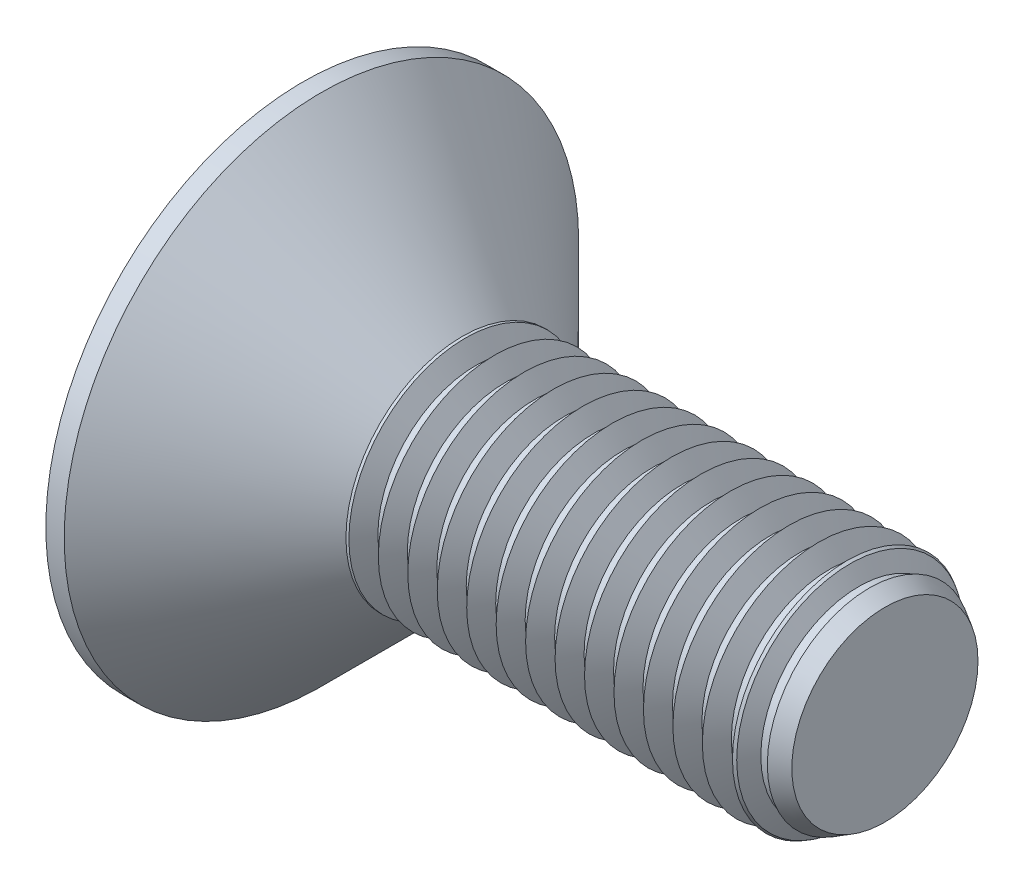
SolidWorks part; units mm, degrees
ref_plane "Front" through (0, 0, 0) normal (0, 0, 1) x (1, 0, 0)
ref_plane "Top" through (0, 0, 0) normal (0, 1, 0) x (1, 0, 0)
ref_plane "Right" through (0, 0, 0) normal (1, 0, 0) x (0, 0, -1)
sketch "Sketch1" plane through (0, 0, 0) normal (0, 0, 1) x (1, 0, 0)
  line L0 (0, 4.2) -> (0.3, 4.2)
  line L1 (0.3, 4.2) -> (2.6, 1.9)
  line L2 (2.6, 1.9) -> (9.5, 1.9)
  line L3 (9.5, 1.9) -> (9.5, 0)
  line L4 (9.5, 0) -> (0, 0)
  line L5 (0, 0) -> (0, 4.2)
  line L6 (6.6207, 0) -> (-0.9387, 0) construction
  dimension "D1" = 45
  dimension "k" = 2.6
revolve "Revolve1" add sketch "Sketch1" angle 360 about L6
cosmetic thread "ThreadCosmetic" [suppressed] parameters "D2"=3.2
chamfer "Chamfer1" distance 0.38 angle 60 1 edges at (9.5, 0, -1.9) first distance on face at (9.5, 0, -1.9)
sketch "Sketch9" plane through (0, 0, 0) normal (0, 0, 1) x (1, 0, 0)
  line L0 (2.9558, 1.6) -> (2.8213, 1.6)
  line L1 (2.8213, 1.6) -> (2.6481, 1.9)
  line L2 (2.9558, 1.6) -> (3.129, 1.9)
  line L3 (2.6481, 1.9) -> (2.6481, 2.15)
  line L4 (3.129, 1.9) -> (3.129, 2.15)
  line L5 (2.6481, 2.15) -> (3.129, 2.15)
  line L6 (2.8886, 1.6) -> (2.8886, 0) construction
  line L7 (0, 0) -> (7.3035, 0) construction
  line L8 (2.6, 1.9) -> (2.6, -1.9) construction
  line L9 (8.8418, 1.9) -> (2.6, 1.9) construction
  dimension "D2" = 60
  dimension "D3" = 0.25
  dimension "minordia" = 3.2
  dimension "threadstart" = 0.2886
revolve "ThreadSchematic" cut sketch "Sketch9" angle 360 about L7
pattern_linear "ThdSchPat" count 15 spacing 0.4809 along (1, 0, 0) of "ThreadSchematic"
sketch "Sketch3" plane through (0, 0, 0) normal (0, 0, 1) x (1, 0, 0)
  line L0 (2.6, 1.9) -> (9.5, 1.9) construction
  line L2 (7.5, 1.9) -> (8, 1.9) construction
  line L3 (9.5, 1.9) -> (9.5, 0) construction
  line L4 (8, 1.9) -> (9.5, 1.9)
  line L5 (2.9, 0) -> (5.4301, 0) construction
  line L6 (9.5, 0) -> (9.7, 0)
  line L7 (9.7, 0) -> (9.7, 1.9)
  line L8 (9.7, 1.9) -> (9.5, 1.9)
  line L9 (8, 1.9) -> (9.5, 0)
  dimension "D1" = 0.5
revolve "EndCone" [suppressed] cut sketch "Sketch3" angle 360 about L5
sketch "Sketch4" plane through (0, 0, 0) normal (-1, 0, 0) x (0, 0, 1)
  line L0 (-0.25, 1) -> (-0.25, 0.25)
  line L1 (-0.25, 1) -> (0.25, 1)
  line L2 (-1, 0.25) -> (-1, -0.25)
  line L3 (-0.25, -1) -> (0.25, -1)
  line L4 (1, 0.25) -> (1, -0.25)
  line L5 (0.25, 1) -> (0.25, 0.25)
  line L6 (0.25, 0.25) -> (1, 0.25)
  line L7 (0.25, -0.25) -> (1, -0.25)
  line L8 (0.25, -0.25) -> (0.25, -1)
  line L9 (-0.25, -0.25) -> (-0.25, -1)
  line L10 (-0.25, -0.25) -> (-1, -0.25)
  line L11 (-0.25, 0.25) -> (-1, 0.25)
  line L12 (1, 0) -> (-1, 0) construction
  dimension "D1" = 0.5
extrude "Cut-Extrude1" cut sketch "Sketch4" against normal blind 1.2
draft "Draft1" type of draft neutral plane draft angle 35 faces to draft 4 face at (0.6, 0, 1) face at (0.6, 1, 0) face at (0.6, 0, -1) face at (0.6, -1, 0) neutral plane through (0, 0, 0) neutral plane normal (-1, 0, 0) parameters "D1"=35
draft "Draft2" type of draft neutral plane draft angle 8 faces to draft 8 face at (0.357, -0.5, -0.25) face at (0.357, -0.25, -0.5) face at (0.357, -0.25, 0.5) face at (0.357, -0.5, 0.25) face at (0.357, 0.5, 0.25) face at (0.357, 0.25, 0.5) face at (0.357, 0.25, -0.5) face at (0.357, 0.5, -0.25) neutral plane through (0, 0, 0) neutral plane normal (-1, 0, 0) parameters "D1"=8
sketch "Sketch6" plane through (1.2, 0, 0) normal (-1, 0, 0) x (0, 0, 1)
  line L0 (0.0814, 0.0814) -> (0.0814, 0.1598) construction
  line L1 (0.1598, 0.0814) -> (0.0814, 0.0814) construction
  line L2 (-0.0814, 0.1598) -> (-0.0814, 0.0814) construction
  line L3 (-0.0814, 0.0814) -> (-0.1598, 0.0814) construction
  line L4 (-0.1598, -0.0814) -> (-0.0814, -0.0814) construction
  line L5 (-0.0814, -0.0814) -> (-0.0814, -0.1598) construction
  line L6 (0.0814, -0.1598) -> (0.0814, -0.0814) construction
  line L7 (0.0814, -0.0814) -> (0.1598, -0.0814) construction
  line L9 (-0.1206, 0.0814) -> (-0.1206, -0.0814)
  line L10 (-0.0814, -0.1206) -> (0.0814, -0.1206)
  line L11 (0.1206, -0.0814) -> (0.1206, 0.0814)
  line L12 (0.0814, 0.1206) -> (-0.0814, 0.1206)
  arc A0 (0.0814, 0.1206) -> (0.1206, 0.0814) centre (0.1206, 0.1206) ccw
  arc A1 (-0.0814, 0.1206) -> (-0.1206, 0.0814) centre (-0.1206, 0.1206) cw
  arc A2 (-0.1206, -0.0814) -> (-0.0814, -0.1206) centre (-0.1206, -0.1206) cw
  arc A3 (0.0814, -0.1206) -> (0.1206, -0.0814) centre (0.1206, -0.1206) cw
sketch "Sketch7" plane through (0, 0, 0) normal (-1, 0, 0) x (0, 0, 1)
  line L8 (0.25, 0.25) -> (0.25, 1) construction
  line L9 (1, 0.25) -> (0.25, 0.25) construction
  line L10 (0.25, -0.25) -> (1, -0.25) construction
  line L11 (0.25, -1) -> (0.25, -0.25) construction
  line L12 (-0.25, 1) -> (-0.25, 0.25) construction
  line L13 (-0.25, 0.25) -> (-1, 0.25) construction
  line L14 (-1, -0.25) -> (-0.25, -0.25) construction
  line L15 (-0.25, -0.25) -> (-0.25, -1) construction
  line L16 (0.2892, 0.25) -> (0.2892, -0.25)
  line L17 (0.25, -0.2892) -> (-0.25, -0.2892)
  line L18 (-0.2892, -0.25) -> (-0.2892, 0.25)
  line L19 (-0.25, 0.2892) -> (0.25, 0.2892)
  arc A0 (0.25, 0.2892) -> (0.2892, 0.25) centre (0.2892, 0.2892) ccw
  arc A1 (-0.25, 0.2892) -> (-0.2892, 0.25) centre (-0.2892, 0.2892) cw
  arc A2 (-0.2892, -0.25) -> (-0.25, -0.2892) centre (-0.2892, -0.2892) cw
  arc A3 (0.0814, 0.1206) -> (0.1206, 0.0814) centre (0.1206, 0.1206) ccw construction
  arc A4 (0.2892, -0.25) -> (0.25, -0.2892) centre (0.2892, -0.2892) ccw
loft "Cut-Loft1" cut profiles "Sketch6", "Sketch7" connector at (1.2, 0.1206, 0.0814) connector at (0, 0.2892, 0.25)
sketch "Sketch8" plane through (0, 0, 0) normal (-1, 0, 0) x (0, 0, 1)
  line L0 (0, 0) -> (1, 1) construction
  line L1 (0.0814, 0.1206) -> (1, 1)
  line L2 (1, 1) -> (0.1206, 0.0814)
  line L3 (0.25, 1) -> (1, 1) construction
  line L4 (1, 1) -> (1, 0.25) construction
  line L5 (0, 0) -> (0.1206, 0) construction
  line L6 (0.1206, 0.0814) -> (0.1206, 0)
  line L7 (0.0814, 0.1206) -> (0, 0.1206)
  line L8 (0, 0.1206) -> (0, 0) construction
  line L9 (0.0814, -0.1206) -> (0, -0.1206)
  line L10 (1, -1) -> (0.0814, -0.1206)
  line L11 (0.1206, -0.0814) -> (1, -1)
  line L12 (0.1206, -0.0814) -> (0.1206, 0)
  line L13 (-0.1206, -0.0814) -> (-0.1206, 0)
  line L14 (-1, -1) -> (-0.1206, -0.0814)
  line L15 (-0.0814, -0.1206) -> (-1, -1)
  line L16 (-0.0814, -0.1206) -> (0, -0.1206)
  line L17 (-0.0814, 0.1206) -> (0, 0.1206)
  line L18 (-1, 1) -> (-0.0814, 0.1206)
  line L19 (-0.1206, 0.0814) -> (-1, 1)
  line L20 (-0.1206, 0.0814) -> (-0.1206, 0)
  arc A1 (0.0814, 0.1206) -> (0.1206, 0.0814) centre (0.1206, 0.1206) ccw construction
  arc A2 (0.0814, 0.1206) -> (0.1206, 0.0814) centre (0.1206, 0.1206) ccw construction
extrude "TypeZ" [suppressed] cut sketch "Sketch8" against normal blind 0.24 draft 3
equation "\"D1@Chamfer1\" = \"d@Sketch1\" / 10"
equation "\"D1@Sketch4\" = \"m@Sketch4\" / 4"
equation "\"D1@TypeZ\" = \"p@Cut-Extrude1\"*0.2"
equation "\"D1@Sketch3\" = \"y@Sketch3\" / 4"
equation "\"threadstart@Sketch9\"=\"advance@Sketch9\"*0.6"
equation "\"D1@ThdSchPat\" = int(((\"l@Sketch1\"-\"k@Sketch1\")/\"advance@Sketch9\") + 0.999)"
equation "\"D3@ThdSchPat\" = \"advance@Sketch9\""
equation "\"minordia@Sketch9\" = \"D2@ThreadCosmetic\""
